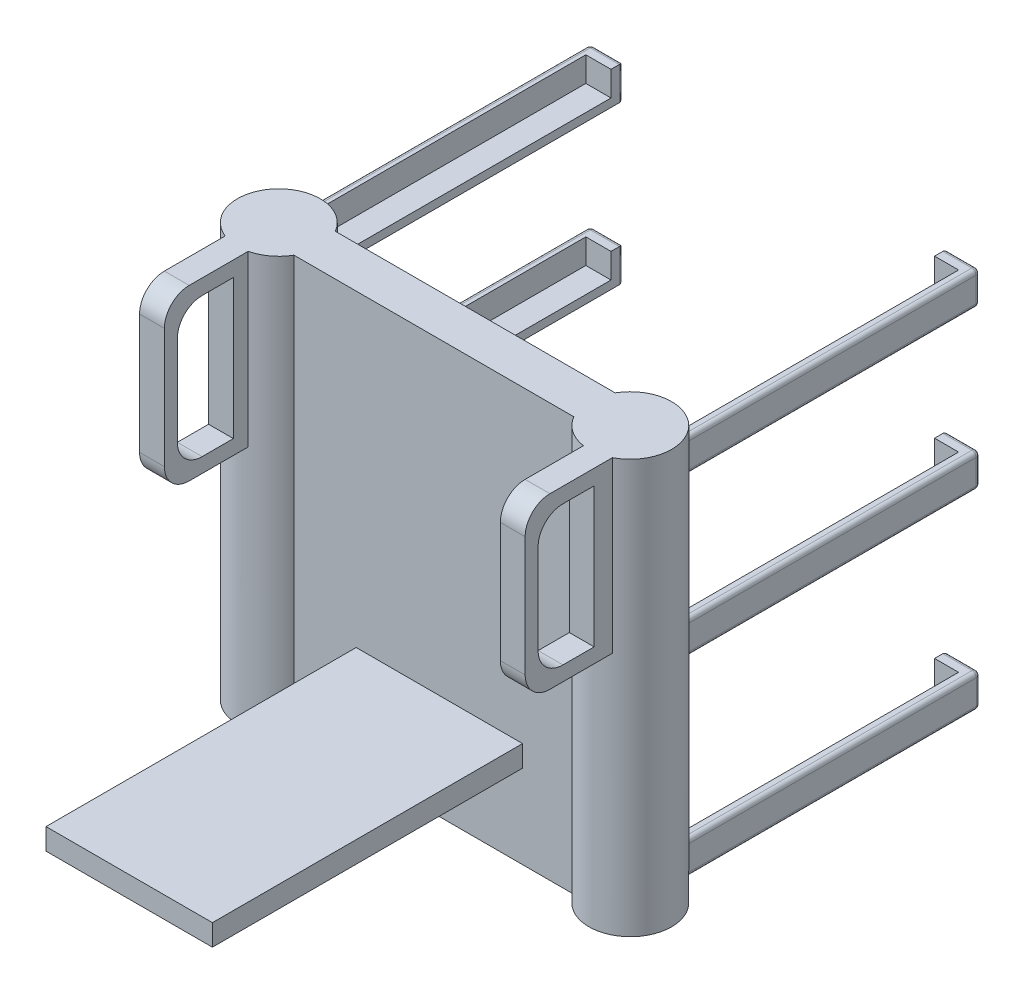
SolidWorks part; units mm, degrees
ref_plane "前视基准面" through (0, 0, 0) normal (0, 0, 1) x (1, 0, 0)
ref_plane "上视基准面" through (0, 0, 0) normal (0, 1, 0) x (1, 0, 0)
ref_plane "右视基准面" through (0, 0, 0) normal (1, 0, 0) x (0, 0, -1)
sketch "草图1" plane through (0, 0, 0) normal (0, 1, 0) x (1, 0, 0)
  line L3 (8.6603, -5) -> (76.3397, -5)
  line L5 (76.3397, 5) -> (8.6603, 5)
  arc A0 (8.6603, 5) -> (8.6603, -5) centre (0, 0) ccw
  arc A1 (76.3397, -5) -> (76.3397, 5) centre (85, 0) ccw
extrude "凸台-拉伸2" add sketch "草图1" along normal blind 100
ref_plane "基准面2" through (0, 0, 30) normal (0, 0, 1) x (1, 0, 0)
sketch "草图4" plane through (0, 0, 30) normal (0, 0, 1) x (1, 0, 0)
  line L0 (-0.6699, 100) -> (2.3301, 100)
  line L2 (2.3301, 100) -> (2.3301, 70)
  line L4 (-3.6699, 70) -> (-3.6699, 100)
  line L5 (-3.6699, 100) -> (2.3301, 100)
  line L6 (85.6699, 100) -> (89.5721, 100)
  line L8 (89.5721, 100) -> (89.5721, 70)
  line L10 (83.5721, 70) -> (83.5721, 100)
  line L11 (83.5721, 100) -> (89.5721, 100)
  line L12 (2.3301, 70) -> (2.3301, 59.0402)
  line L13 (2.3301, 59.0402) -> (-3.6699, 59.0402)
  line L14 (-3.6699, 59.0402) -> (-3.6699, 70)
  line L15 (89.5721, 70) -> (89.5721, 59.0402)
  line L16 (89.5721, 59.0402) -> (83.5721, 59.0402)
  line L17 (83.5721, 59.0402) -> (83.5721, 70)
extrude "凸台-拉伸3" add sketch "草图4" against normal up to body separate body contours L14 L13 L12 L2 L0 L5 L4 | L17 L16 L15 L8 L6 L11 L10 region at (-0.6699, 79.5201, 30) region at (86.5721, 79.5201, 30)
ref_plane "基准面3" through (-30, 0, 0) normal (1, 0, 0) x (0, 0, -1)
sketch "草图5" plane through (-30, 0, 0) normal (1, 0, 0) x (0, 0, -1)
  line L0 (-13.318, 96.3132) -> (-26.8663, 96.3132)
  line L1 (-26.8663, 96.3132) -> (-26.8663, 62.5806)
  line L2 (-26.8663, 62.5806) -> (-13.318, 62.5806)
  line L3 (-13.318, 62.5806) -> (-13.318, 96.3132)
extrude "切除-拉伸1" cut sketch "草图5" along normal through all
fillet "圆角1" radius 6 8 edges at (-0.6699, 62.5806, 26.8663) (86.5721, 62.5806, 26.8663) (86.5721, 96.3132, 26.8663) (-0.6699, 96.3132, 26.8663) (-0.6699, 59.0402, 30) (86.5721, 59.0402, 30) (-0.6699, 100, 30) (86.5721, 100, 30)
ref_plane "基准面4" through (0, 0, -10) normal (0, 0, 1) x (1, 0, 0)
sketch "草图6" plane through (0, 0, -10) normal (0, 0, 1) x (1, 0, 0)
  line L1 (3.3301, 3.0028) -> (-4.6699, 3.0028)
  line L2 (3.3301, 95.252) -> (-4.6699, 95.252)
  line L4 (89.6669, 3.0028) -> (89.5767, 95.252)
  line L6 (81.5721, 3.0028) -> (81.5721, 95.252)
  line L9 (-4.6699, 95.252) -> (-4.6699, 3.0028)
  line L12 (3.3301, 3.0028) -> (3.3301, 95.252)
  line L14 (89.5767, 95.252) -> (81.5721, 95.252)
  line L15 (89.6669, 3.0028) -> (81.5721, 3.0028)
extrude "切除-拉伸2" cut sketch "草图6" along normal blind 10
ref_plane "基准面5" through (0, 0, -80) normal (0, 0, 1) x (1, 0, 0)
sketch "草图7" plane through (0, 0, -80) normal (0, 0, 1) x (1, 0, 0)
  line L0 (89.6669, 3.0028) -> (81.5721, 3.0028)
  line L1 (81.5721, 3.0028) -> (81.5721, 11.0028)
  line L3 (81.5721, 11.0028) -> (89.6591, 11.0028)
  line L5 (89.6591, 11.0028) -> (89.6669, 3.0028)
  line L6 (3.3301, 3.0028) -> (-4.6699, 3.0028)
  line L7 (-4.6699, 3.0028) -> (-4.6699, 11.0028)
  line L9 (-4.6699, 11.0028) -> (3.3301, 11.0028)
  line L11 (3.3301, 11.0028) -> (3.3301, 3.0028)
  line L12 (89.6218, 49.1274) -> (81.5721, 49.1274)
  line L15 (81.5721, 49.1274) -> (81.5721, 57.1274)
  line L16 (89.614, 57.1274) -> (89.6218, 49.1274)
  line L17 (89.614, 57.1274) -> (81.5721, 57.1274)
  line L18 (-4.6699, 49.1274) -> (3.3301, 49.1274)
  line L21 (3.3301, 49.1274) -> (3.3301, 57.1274)
  line L22 (3.3301, 57.1274) -> (-4.6699, 57.1274)
  line L23 (-4.6699, 57.1274) -> (-4.6699, 49.1274)
  line L24 (-4.6699, 95.252) -> (3.3301, 95.252)
  line L25 (3.3301, 95.252) -> (3.3301, 87.252)
  line L26 (3.3301, 87.252) -> (-4.6699, 87.252)
  line L27 (-4.6699, 87.252) -> (-4.6699, 95.252)
  line L28 (81.5721, 95.252) -> (89.5767, 95.252)
  line L29 (89.5767, 95.252) -> (89.5845, 87.252)
  line L30 (89.5845, 87.252) -> (81.5721, 87.252)
  line L31 (81.5721, 87.252) -> (81.5721, 95.252)
extrude "凸台-拉伸4" add sketch "草图7" along normal blind 80
ref_plane "基准面6" through (0, 0, -77) normal (0, 0, 1) x (1, 0, 0)
sketch "草图8" plane through (0, 0, -77) normal (0, 0, 1) x (1, 0, 0)
  line L0 (81.5721, 95.252) -> (81.5721, 89.252)
  line L2 (81.5721, 89.252) -> (87.3828, 89.252)
  line L3 (87.3828, 95.252) -> (87.3828, 89.252)
  line L5 (87.3828, 95.252) -> (81.5721, 95.252)
  line L6 (3.3301, 95.252) -> (3.3301, 89.252)
  line L8 (3.3301, 89.252) -> (-2.755, 89.252)
  line L9 (-2.755, 89.252) -> (-2.755, 95.252)
  line L11 (-2.755, 95.252) -> (3.3301, 95.252)
  line L12 (87.3828, 57.1274) -> (87.3828, 51.1274)
  line L14 (87.3828, 51.1274) -> (81.5721, 51.1274)
  line L16 (81.5721, 51.1274) -> (81.5721, 57.1274)
  line L17 (81.5721, 57.1274) -> (87.3828, 57.1274)
  line L18 (87.3828, 11.0028) -> (87.3828, 5.0028)
  line L20 (81.5721, 11.0028) -> (81.5721, 5.0028)
  line L22 (81.5721, 7.0028) -> (81.5721, 11.0028)
  line L23 (81.5721, 11.0028) -> (87.3828, 11.0028)
  line L25 (81.5721, 5.0028) -> (87.3828, 5.0028)
  line L26 (-2.755, 57.1274) -> (-2.755, 51.1274)
  line L28 (-2.755, 51.1274) -> (3.3301, 51.1274)
  line L30 (3.3301, 51.1274) -> (3.3301, 57.1274)
  line L31 (3.3301, 57.1274) -> (-2.755, 57.1274)
  line L32 (-2.755, 11.0028) -> (-2.755, 5.0028)
  line L34 (-2.755, 5.0028) -> (3.3301, 5.0028)
  line L36 (3.3301, 5.0028) -> (3.3301, 11.0028)
  line L37 (3.3301, 11.0028) -> (-2.755, 11.0028)
extrude "切除-拉伸3" cut sketch "草图8" along normal blind 70 contours L3 L5 L0 L2 | L17 L16 L14 L12 | L20 L25 L18 L23 | L36 L37 L32 L34 | L30 L31 L26 L28 | L11 L6 L8 L9 region at (84.4775, 92.252, -77) region at (84.4775, 54.1274, -77) region at (84.4775, 8.0028, -77) region at (0.2875, 54.1274, -77) region at (0.2875, 8.0028, -77)
fillet "圆角2" radius 1 18 edges at (89.5806, 91.252, -80) (89.6179, 53.1274, -80) (89.663, 7.0028, -80) (-4.6699, 7.0028, -80) (-4.6699, 91.252, -80) (-4.6699, 53.1274, -80) (-4.6699, 87.252, -44.4213) (-4.6699, 49.1274, -44.4213) (-4.6699, 3.0028, -44.4213) (-4.6699, 11.0028, -44.4213) (-4.6699, 57.1274, -44.4213) (-4.6699, 95.252, -44.4213) (89.5845, 87.252, -44.4436) (89.6218, 49.1274, -44.4339) (89.6669, 3.0028, -44.4221) (89.6591, 11.0028, -44.4242) (89.614, 57.1274, -44.436) (89.5767, 95.252, -44.4456)
fillet "圆角3" radius 1 30 edges at (89.3738, 3.2964, -79.7071) (89.3669, 10.7103, -79.7068) (89.3286, 49.421, -79.7071) (89.3217, 56.8349, -79.7068) (-4.377, 94.9591, -79.7071) (-4.377, 87.5449, -79.7071) (-4.377, 10.7099, -79.7071) (-4.377, 3.2957, -79.7071) (-4.377, 56.8345, -79.7071) (-4.377, 49.4203, -79.7071) (89.2914, 87.5456, -79.7071) (89.2845, 94.9595, -79.7068) (81.5721, 7.0028, -80) (85.119, 3.0028, -80) (85.1156, 11.0028, -80) (81.5721, 53.1274, -80) (85.0965, 49.1274, -80) (85.093, 57.1274, -80) (3.3301, 91.252, -80) (-0.1699, 95.252, -80) (-0.1699, 87.252, -80) (3.3301, 7.0028, -80) (-0.1699, 11.0028, -80) (-0.1699, 3.0028, -80) (3.3301, 53.1274, -80) (-0.1699, 57.1274, -80) (-0.1699, 49.1274, -80) (81.5721, 91.252, -80) (85.0778, 87.252, -80) (85.0744, 95.252, -80)
scale "缩放比例1" scale about centroid uniform scaling yes scale factor 0.4
sketch "草图10" plane through (0, 0, 0.0574) normal (0, 0, 1) x (1, 0, 0)
  line L1 (35.076, 40.746) -> (51.1717, 40.746)
  line L2 (35.076, 40.746) -> (35.076, 38.6873)
  line L3 (35.076, 38.6873) -> (51.1717, 38.6873)
  line L4 (51.1717, 40.746) -> (51.1717, 38.6873)
extrude "凸台-拉伸5" add sketch "草图10" along normal blind 30
